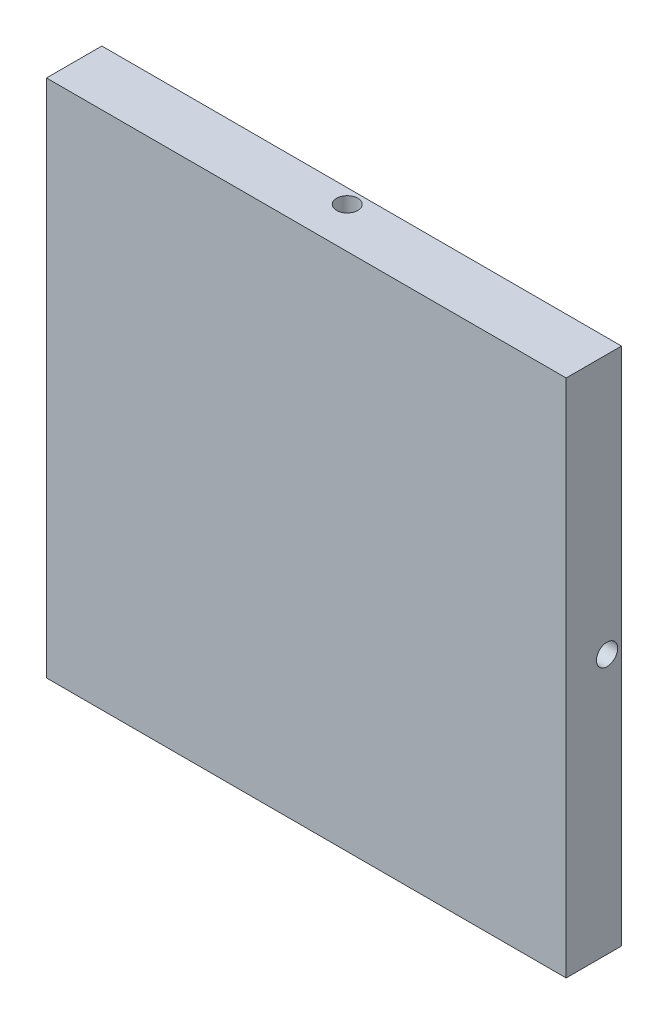
SolidWorks part; units mm, degrees
ref_plane "Front Plane" through (0, 0, 0) normal (0, 0, 1) x (1, 0, 0)
ref_plane "Top Plane" through (0, 0, 0) normal (0, 1, 0) x (1, 0, 0)
ref_plane "Right Plane" through (0, 0, 0) normal (1, 0, 0) x (0, 0, -1)
sketch "Sketch1" plane through (0, 0, 0) normal (0, 0, 1) x (1, 0, 0)
  line L1 (-85.725, 85.725) -> (85.725, 85.725)
  line L2 (-85.725, 85.725) -> (-85.725, -85.725)
  line L3 (-85.725, -85.725) -> (85.725, -85.725)
  line L4 (85.725, 85.725) -> (85.725, -85.725)
  line L5 (0, 0) -> (0, -76.9938) construction
  line L6 (-27.4443, 76.9938) -> (31.5245, 76.9938) construction
  circle A0 centre (0, 0) radius 76.9938
  circle A2 centre (0, 0) radius 3.3
  circle A5 centre (-73.025, 73.025) radius 3.175
  circle A6 centre (73.025, 73.025) radius 3.175
  circle A7 centre (73.025, -73.025) radius 3.175
  circle A8 centre (-73.025, -73.025) radius 3.175
  circle A9 centre (0, 25.4) radius 1.543
  point P9 (0, 0)
  point P12 (0, 85.725)
  point P18 (0, 0)
  point P23 (-85.725, 0)
  point P29 (0, 0)
  dimension "D1" = 153.9875
  dimension "D5" = 6.6
  dimension "D7" = 6.35
  dimension "D2" = 3.0861
  dimension "D3" = 25.4
  dimension "D8" = 12.7
  dimension "D9" = 90
  dimension "D10" = 12.7
  dimension "D11" = 4
  dimension "D12" = 85.725
  dimension "D13" = 8.7312
extrude "Boss-Extrude1" add sketch "Sketch1" along normal blind 8.7312 contours L4 L1 L2 L3 A8 A7 A6 A5 A0 | A6 | A5 | A8 | A7 | A0 A2 | A2 region at (0, 83.3003, 0) region at (-74.816, 0, 0) region at (0, 0, 0) region at (-73.025, 73.025, 0) region at (73.025, 73.025, 0) region at (73.025, -73.025, 0) region at (-73.025, -73.025, 0)
extrude "Boss-Extrude2" add sketch "Sketch1<3>" against normal blind 9.525 contours L4 L1 L2 L3 A8 A7 A6 A5 A0 | A2 region at (0, 83.3003, 0) region at (0, 0, 0)
sketch "Sketch1<3>" plane through (0, 0, 0) normal (0, 0, 1) x (1, 0, 0) same geometry as "Sketch1"
extrude "Boss-Extrude3" add sketch "Sketch1<4>" against normal blind 18.3515 contours A2 region at (0, 0, 0)
sketch "Sketch1<4>" plane through (0, 0, 0) normal (0, 0, 1) x (1, 0, 0) same geometry as "Sketch1"
sketch "Sketch2" plane through (0, 85.725, 0) normal (0, 1, 0) x (1, 0, 0)
  line L0 (-85.725, 9.525) -> (85.725, 9.525) construction
  circle A0 centre (0, 4.7625) radius 3.5
  dimension "D1" = 7
  dimension "D2" = 4.7625
extrude "Cut-Extrude1" cut sketch "Sketch2" against normal up to next
pattern_circular "CirPattern1" count 4 over 360 about axis through (0, 0, -9.525) along (0, 0, 1) of "Cut-Extrude1"
extrude "Boss-Extrude4" add sketch "Sketch1<5>" against normal blind 9.525 and the other way up to surface (8.7312 mm away) contours A9 region at (0, 25.4, 0) other way up to face at (0, 0, 8.7312)
sketch "Sketch1<5>" plane through (0, 0, 0) normal (0, 0, 1) x (1, 0, 0) same geometry as "Sketch1"
